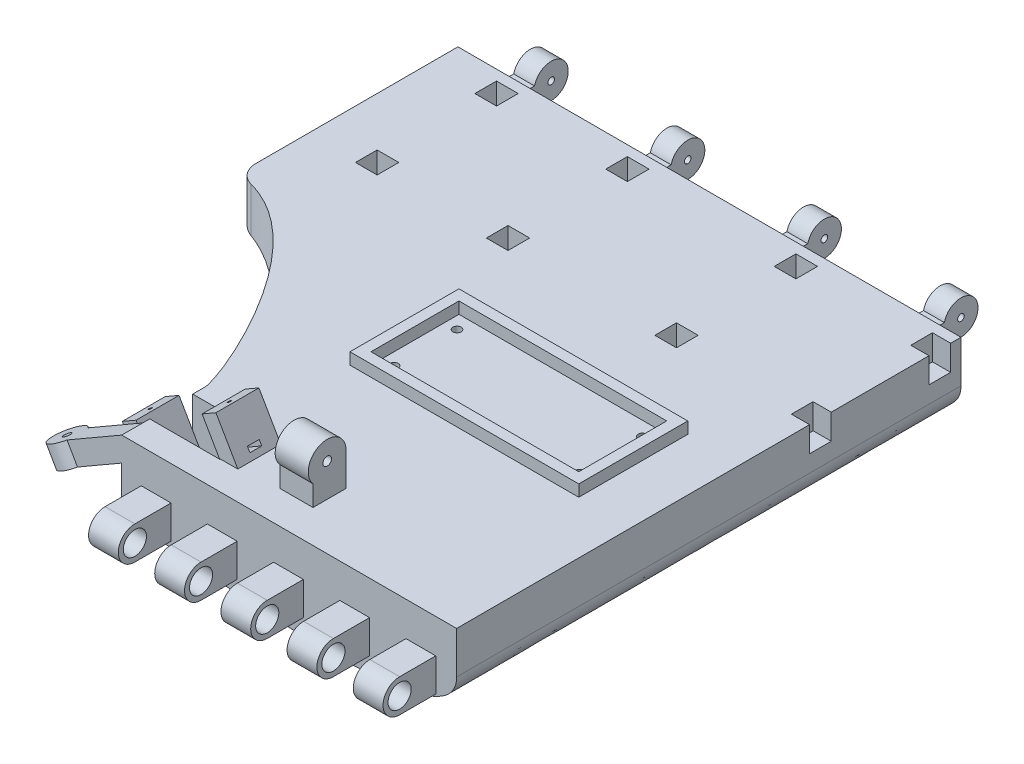
SolidWorks part; units mm, degrees
material "ABS"
ref_plane "Front Plane" through (0, 0, 0) normal (0, 0, 1) x (1, 0, 0)
ref_plane "Top Plane" through (0, 0, 0) normal (0, 1, 0) x (1, 0, 0)
ref_plane "Right Plane" through (0, 0, 0) normal (1, 0, 0) x (0, 0, -1)
sketch "Sketch2" plane through (0, 0, 0) normal (0, 1, 0) x (1, 0, 0)
  line L0 (0, 0) -> (-152, 0)
  line L1 (-152, 0) -> (-152, -152.4)
  line L2 (-152, -152.4) -> (0, -152.4)
  line L3 (0, -152.4) -> (0, 0)
  dimension "D1" = 152.4
  dimension "D2" = 152
extrude "Boss-Extrude2" add sketch "Sketch2" along normal blind 12.7
ref_plane "Plane2" through (-14.9327, 0, 0) normal (1, 0, 0) x (0, 0, -1)
ref_plane "Plane1" through (-12.7, 0, 0) normal (1, 0, 0) x (0, 0, -1)
sketch "Sketch9" plane through (0, 12.7, 0) normal (0, 1, 0) x (1, 0, 0)
  line L0 (0, 0) -> (0, -48.862) construction
  line L1 (0, -152.4) -> (0, 0) construction
  line L2 (-152, 0) -> (-152, -48.862) construction
  line L3 (-152, 0) -> (-152, -152.4) construction
  line L4 (0, 0) -> (-5.4077, 0) construction
  line L5 (0, 0) -> (-152, 0) construction
  dimension "D1" = 48.862
  dimension "D2" = 48.862
  dimension "D3" = 5.4077
ref_axis "Axis2" through (-152, 12.7, 48.862) along (1, 0, 0)
sketch "Sketch3" plane through (-12.7, 0, 0) normal (1, 0, 0) x (0, 0, -1)
  line L0 (0, 6.35) -> (0, 0)
  line L2 (0, 12.7) -> (0, 0) construction
  line L3 (0, 0) -> (12.7, 0)
  line L4 (12.7, 6.1562) -> (12.7, 6.1587)
  line L5 (7.6839, 6.35) -> (0, 6.35)
  arc A3 (12.7, 0) -> (7.6839, 6.35) centre (12.7, 5.1562) ccw
  circle A5 centre (12.7, 5.1562) radius 1
  dimension "D3" = 10.3124
  dimension "D2" = 0
  dimension "D4" = 7.6839
  dimension "D6" = 2
  dimension "D1" = 6.35
  dimension "D5" = 12.7
extrude "Boss-Extrude3" add sketch "Sketch3" against normal blind 6.3 contours A5 L4 L3 A3 | A5 L4 A3 L3 | A3 L5 L0 L3 region at (-12.7, 4.2781, -9.3369)
ref_plane "Plane5" through (0, 0, 24.431) normal (0, 0, -1) x (-1, 0, 0)
ref_plane "Plane6" through (0, 12.7, 0) normal (0, 1, 0) x (1, 0, 0)
sketch "Sketch10" plane through (0, 12.7, 0) normal (0, 1, 0) x (1, 0, 0)
  line L0 (0, 0) -> (-152, 0) construction
  circle A0 centre (-10.2337, -3.175) radius 0.508
  dimension "D1" = 10.2337
  dimension "D3" = 1.016
  dimension "D2" = 3.175
extrude "Cut-Extrude3" [suppressed] cut sketch "Sketch10" against normal blind 9.525
mirror "Mirror1" [suppressed] about plane through (0, 0, 24.431) normal (0, 0, -1)
fillet "Fillet1" radius 1.5875 3 edges at (-19, 3.175, 0) (-15.85, 6.35, 0) (-12.7, 3.175, 0)
pattern_linear "LPattern1" count 4 spacing 41.275 along (-1, 0, 0) of "Boss-Extrude3", "Mirror1", "Fillet1"
sketch "Sketch12" plane through (0, 0, 0) normal (0, 0, -1) x (-1, 0, 0)
  spline S0 degree 1 poles (0, 0) (152, 0) knots 0 0 1 1
  spline S1 degree 2 poles (152, 0) (-0.2287, -25.399) (0, 0) knots 0 0 0 0.553499 0.553499 0.553499
  spline S2 degree 1 poles (0, 0) (152, 0) knots 0 0 1 1
  spline S3 degree 1 poles (152, 0) (0, 0) knots 0 0 1 1
  dimension "D1" = 50.8
extrude "Boss-Extrude4" add sketch "Sketch12" against normal up to surface (152.4 mm away) contours S1 | S0 S1 up to face at (-76, 6.35, 152.4)
sketch "Sketch13" plane through (0, 12.7, 0) normal (0, 1, 0) x (1, 0, 0)
  line L0 (0, -152.4) -> (0, 0) construction
  line L1 (-81.8426, -69.85) -> (-19.05, -69.85)
  line L2 (-81.8426, -69.85) -> (-81.8426, -96.44)
  line L3 (-81.8426, -96.44) -> (-19.05, -96.44)
  line L4 (-19.05, -69.85) -> (-19.05, -96.44)
  line L5 (0, 0) -> (-152, 0) construction
  line L7 (-85.0176, -66.675) -> (-15.875, -66.675)
  line L8 (-85.0176, -66.675) -> (-85.0176, -99.615)
  line L9 (-85.0176, -99.615) -> (-15.875, -99.615)
  line L10 (-15.875, -66.675) -> (-15.875, -99.615)
  dimension "D1" = 62.7926
  dimension "D2" = 26.59
  dimension "D3" = 19.05
  dimension "D4" = 69.85
  dimension "D5" = 3.175
  dimension "D6" = 3.175
  dimension "D7" = 3.175
  dimension "D8" = 3.175
extrude "Boss-Extrude5" add sketch "Sketch13" along normal blind 3.5001
sketch "Sketch14" plane through (0, 12.7, 0) normal (0, 1, 0) x (1, 0, 0)
  line L0 (-19.05, -69.85) -> (-81.8426, -69.85) construction
  line L1 (-81.8426, -69.85) -> (-81.8426, -96.44) construction
  circle A0 centre (-78.1761, -74.1223) radius 1.2497
  circle A1 centre (-22.1767, -74.1223) radius 1.2497
  circle A2 centre (-78.1761, -93.1215) radius 1.2497
  circle A3 centre (-22.1767, -93.1215) radius 1.2497
  dimension "D1" = 4.2723
  dimension "D3" = 3.6665
  dimension "D4" = 55.9994
  dimension "D2" = 18.9992
extrude "Cut-Extrude5" cut sketch "Sketch14" against normal blind 6.35
sketch "Sketch15" plane through (0, 12.7, 0) normal (0, 1, 0) x (1, 0, 0)
  line L0 (-101.2, -152.4) -> (-101.2, -127)
  line L1 (-152, -152.4) -> (0, -152.4) construction
  line L2 (-101.2, -127) -> (-152, -66.4589)
  line L3 (-152, 0) -> (-152, -152.4) construction
  line L4 (-152, -66.4589) -> (-152, -152.4)
  line L5 (-152, -152.4) -> (-101.2, -152.4)
  spline S0 degree 3 poles (-101.2, -127) (-102.2273, -119.2728) (-124.4228, -68.0569) (-152, -66.4589) knots 0 0 0 0 0.841715 0.841715 0.841715 0.841715
  line M9 (-152, 0) -> (-152, -152.4)
  line M10 (-152, -152.4) -> (0, -152.4)
  dimension "D1" = 50.8
  dimension "D2" = 25.4
  dimension "D3" = 220
extrude "Cut-Extrude6" cut sketch "Sketch15" against normal through all contours L2 S0 | L0 L2 M9 M10 region at (-131.2037, 12.7, 121.8215) region at (-125.4187, 12.7, 91.8783)
sketch "Sketch16" plane through (0, 0, 152.4) normal (0, 0, 1) x (1, 0, 0)
  line L0 (-101.2, 12.7) -> (-101.2, 5.3677)
  line L1 (-101.2, 12.7) -> (-117.6978, 3.175)
  line L2 (-101.2, 5.3677) -> (-117.6978, -4.1573)
  line L3 (-117.6978, 3.175) -> (-117.6978, -4.1573)
  line L4 (-101.2, -7.6194) -> (-101.2, 12.7) construction
  dimension "D1" = 6.35
  dimension "D2" = 60
  dimension "D3" = 19.05
extrude "Boss-Extrude6" add sketch "Sketch16" against normal blind 6.35
sketch "Sketch17" plane through (-27.6243, 47.8466, 0) normal (0.5, -0.866, 0) x (0.866, 0.5, 0)
  line L0 (-104.0079, 146.05) -> (-104.0079, 152.4) construction
  circle A0 centre (-104.0079, 149.225) radius 4.826
  dimension "D1" = 9.652
extrude "Boss-Extrude7" add sketch "Sketch17" against normal up to surface (6.35 mm away) up to face at (-109.4489, 7.9375, 149.225)
sketch "Sketch18" plane through (-27.6243, 47.8466, 0) normal (0.5, -0.866, 0) x (0.866, 0.5, 0)
  circle A0 centre (-104.0079, 149.225) radius 1.143
  dimension "D1" = 2.286
extrude "Cut-Extrude8" cut sketch "Sketch18" against normal up to surface (6.35 mm away) up to face at (-113.4243, 5.6423, 149.225)
ref_plane "Plane7" through (-30.7993, 53.3459, 0) normal (-0.5, 0.866, 0) x (0.866, 0.5, 0)
sketch "Sketch20" plane through (-30.7993, 53.3459, 0) normal (-0.5, 0.866, 0) x (0.866, 0.5, 0)
  line L0 (-86.0567, -130.9381) -> (-86.0567, -143.9239)
  line L1 (-86.0567, -143.9239) -> (-62.911, -143.9239)
  line L2 (-62.911, -143.9239) -> (-62.911, -130.9381)
  line L3 (-62.911, -130.9381) -> (-86.0567, -130.9381)
  dimension "D1" = 12.9857
  dimension "D2" = 23.1457
extrude "Cut-Extrude9" cut sketch "Sketch20" against normal blind 15.494
sketch "Sketch21" plane through (-30.7993, 53.3459, 0) normal (-0.5, 0.866, 0) x (0.866, 0.5, 0)
  line L0 (-86.0373, -130.9653) -> (-90.8633, -130.9653)
  line L1 (-90.8633, -130.9653) -> (-90.8633, -143.951)
  line L2 (-90.8633, -143.951) -> (-86.0373, -143.951)
  line L3 (-86.0373, -143.951) -> (-86.0373, -130.9653)
  line L4 (-63.2251, -143.7536) -> (-58.3991, -143.7536)
  line L5 (-58.3991, -143.7536) -> (-58.3991, -130.7678)
  line L6 (-58.3991, -130.7678) -> (-63.2251, -130.7678)
  line L7 (-63.2251, -130.7678) -> (-63.2251, -143.7536)
  line L8 (6.35, -152.4) -> (6.35, 0) construction
  dimension "D1" = 12.9857
  dimension "D2" = 12.9857
  dimension "D3" = 4.826
  dimension "D4" = 22.8122
  dimension "D5" = 4.826
  dimension "D6" = 64.7491
extrude "Boss-Extrude8" add sketch "Sketch21" against normal up to surface (18.046 mm away) up to face at (-89.1246, -1.8694, 79.9709)
sketch "Sketch22" plane through (-30.7993, 53.3459, 0) normal (-0.5, 0.866, 0) x (0.866, 0.5, 0)
  circle A0 centre (-88.4503, -137.587) radius 0.508
  circle A1 centre (-60.8121, -137.587) radius 0.508
  dimension "D1" = 1.016
  dimension "D2" = 1.016
extrude "Cut-Extrude10" cut sketch "Sketch22" against normal blind 10.16
sketch "Esquisse1" plane through (0, 0, 152.4) normal (0, 0, 1) x (1, 0, 0)
  line L0 (-78.1, 4.563) -> (-78.1, 7.7177)
  line L1 (-74.3, 4.1474) -> (-74.3, 7.7177)
  line L2 (-78.1, 4.563) -> (-92.8263, 3.2599)
  line L3 (-92.8263, -0.7245) -> (-78.1, -2.0277)
  line L4 (-78.1, -2.0277) -> (-78.1, -5.1823)
  line L5 (-74.3, -5.1823) -> (-74.3, -1.612)
  line L6 (-73.9909, -1.3823) -> (-62.0409, -0.7293)
  line L7 (-73.9909, 3.9177) -> (-62.0409, 3.2647)
  arc A0 (-78.1, 7.7177) -> (-74.3, 7.7177) centre (-76.2, 7.7177) cw
  arc A2 (-62.0409, 3.2647) -> (-62.0409, -0.7293) centre (-62.15, 1.2677) cw
  arc A3 (-92.8263, 3.2599) -> (-92.8263, -0.7245) centre (-92.65, 1.2677) ccw
  arc A4 (-78.1, -5.1823) -> (-74.3, -5.1823) centre (-76.2, -5.1823) ccw
  arc A5 (-74.3, 4.1474) -> (-73.9909, 3.9177) centre (-76.2, 1.2677) cw
  arc A6 (-73.9909, -1.3823) -> (-74.3, -1.612) centre (-76.2, 1.2677) cw
fillet "Fillet2" radius 6.35 2 edges at (-101.2, 2.5403, 127) (-152, 6.35, 66.4589)
sketch "Sketch23" plane through (-50.5751, -29.1996, 0) normal (0.866, 0.5, 0) x (0, 0, -1)
  line L0 (-139.1816, 51.6925) -> (-139.1816, 50.1685)
  line L1 (-139.1816, 50.1685) -> (-135.6256, 50.1685)
  line L2 (-135.6256, 50.1685) -> (-135.6256, 51.6925)
  line L3 (-135.6256, 51.6925) -> (-139.1816, 51.6925)
  line L4 (-143.7536, 61.5985) -> (-130.7678, 61.5985) construction
  line L5 (-143.7536, 48.3814) -> (-143.7536, 61.5985) construction
  dimension "D1" = 9.906
  dimension "D2" = 4.572
  dimension "D3" = 3.556
  dimension "D4" = 1.524
extrude "Cut-Extrude11" cut sketch "Sketch23" against normal up to surface (4.826 mm away) up to face at (-81.233, 14.2495, 135.1532)
sketch "Esquisse5" plane through (0, 12.7, 0) normal (0, 1, 0) x (1, 0, 0)
  line L0 (-130.7715, -45.6452) -> (-137.1215, -45.6452) construction
  line L1 (-137.1215, -45.6452) -> (-137.1215, -39.2952) construction
  line L2 (-137.1215, -39.2952) -> (-130.7715, -39.2952) construction
  line L3 (-130.7715, -39.2952) -> (-130.7715, -45.6452) construction
  line L4 (-130.7715, -9.5674) -> (-137.1215, -9.5674) construction
  line L5 (-137.1215, -9.5674) -> (-137.1215, -3.2174) construction
  line L6 (-137.1215, -3.2174) -> (-130.7715, -3.2174) construction
  line L7 (-130.7715, -3.2174) -> (-130.7715, -9.5674) construction
  line L8 (-130.7715, -45.6452) -> (-137.1215, -45.6452) construction
  line L9 (-137.1215, -45.6452) -> (-137.1215, -39.2952) construction
  line L10 (-137.1215, -39.2952) -> (-130.7715, -39.2952) construction
  line L11 (-130.7715, -39.2952) -> (-130.7715, -45.6452) construction
  line L12 (-130.7715, -9.5674) -> (-137.1215, -9.5674) construction
  line L13 (-137.1215, -9.5674) -> (-137.1215, -3.2174) construction
  line L14 (-137.1215, -3.2174) -> (-130.7715, -3.2174) construction
  line L15 (-130.7715, -3.2174) -> (-130.7715, -9.5674) construction
  line L16 (-137.2215, -3.1174) -> (-130.6715, -3.1174)
  line L17 (-130.6715, -3.1174) -> (-130.6715, -9.6674)
  line L18 (-130.6715, -9.6674) -> (-137.2215, -9.6674)
  line L19 (-137.2215, -9.6674) -> (-137.2215, -3.1174)
  line L20 (-137.2215, -39.1952) -> (-130.6715, -39.1952)
  line L21 (-130.6715, -39.1952) -> (-130.6715, -45.7452)
  line L22 (-130.6715, -45.7452) -> (-137.2215, -45.7452)
  line L23 (-137.2215, -45.7452) -> (-137.2215, -39.1952)
  dimension "D1" = 0.1
extrude "Enlèv. mat.-Extru.3" cut sketch "Esquisse5" against normal blind 7.62
sketch "Esquisse6" plane through (0, 0, 152.4) normal (0, 0, 1) x (1, 0, 0)
  line L5 (-55.3, -7.62) -> (-46.3, -7.62)
  line L6 (-55.3, -7.62) -> (-55.3, 2.38)
  line L7 (-55.3, 2.38) -> (-46.3, 2.38)
  line L8 (-46.3, -7.62) -> (-46.3, 2.38)
  line L10 (0, 12.7) -> (0, 0) construction
  point P9 (-50.8, 2.38)
  dimension "D1" = 9
  dimension "D2" = 10
  dimension "D3" = 7.62
  dimension "D4" = 50.8
extrude "Boss.-Extru.1" add sketch "Esquisse6" along normal blind 10.922
sketch "Esquisse7" plane through (-55.3, 0, 0) normal (-1, 0, 0) x (0, 0, 1)
  line L1 (163.322, 2.38) -> (163.322, -7.62) construction
  circle A0 centre (163.322, -2.62) radius 5
extrude "Boss.-Extru.2" add sketch "Esquisse7" against normal up to surface (9 mm away) up to face at (-46.3, -2.62, 157.861)
hole_wizard "Dégagement M21" positions "Esquisse8" profile "Esquisse9" hole size "M2" standard "Ansi Metric" end condition up to next
sketch "Esquisse8" plane through (-55.3, 0, 0) normal (-1, 0, 0) x (0, 0, 1)
  line L1 (152.4, 2.38) -> (152.4, -7.62) construction
  point P0 (163.322, -2.62)
  point P15 (152.4, -2.62)
sketch "Esquisse9" plane through (-55.3, -2.62, 163.322) normal (0, 1, 0) x (0, 0, 1)
  line L0 (0, 0) -> (0, 9)
  line L1 (0, 9) -> (3.5, 9)
  line L2 (3.5, 9) -> (3.5, 0)
  line L5 (3.5, 0) -> (0, 0)
  line L11 (0, -6.35) -> (0, 107.95) construction
  dimension "Diamètre du perçage jusqu'au prochain" = 7
  dimension "Profondeur du perçage jusqu'au prochain" = 9
pattern_linear "Répétition linéaire1" count 3 spacing 20 along (1, 0, 0) count 3 spacing 20 along (-1, 0, 0) of "Boss.-Extru.1", "Dégagement M21", "Boss.-Extru.2" pattern seed only yes
sketch "Esquisse10" plane through (0, 12.7, 0) normal (0, -1, 0) x (1, 0, 0)
  line L1 (-53.34, 142.4581) -> (-63.34, 142.4581)
  line L2 (-53.34, 142.4581) -> (-53.34, 132.4581)
  line L3 (-53.34, 132.4581) -> (-63.34, 132.4581)
  line L4 (-63.34, 142.4581) -> (-63.34, 132.4581)
  line L5 (-55.3, 152.4) -> (-46.3, 152.4) construction
  line L6 (-101.2, 143.951) -> (-101.2, 130.9653) construction
  point P4 (-63.34, 137.4581)
  point P8 (-50.8, 152.4)
  point P10 (-101.2, 137.4581)
  dimension "D1" = 10
  dimension "D2" = 10
  dimension "D3" = 2.54
extrude "Boss.-Extru.3" add sketch "Esquisse10" against normal blind 10
sketch "Esquisse11" plane through (-53.34, 0, 0) normal (1, 0, 0) x (0, 0, -1)
  line L0 (-132.4581, 22.7) -> (-142.4581, 22.7) construction
  circle A0 centre (-138.1731, 22.7) radius 5.715
  dimension "D1" = 11.43
extrude "Boss.-Extru.4" add sketch "Esquisse11" against normal up to surface (10 mm away) up to face at (-63.34, 17.7, 137.4581)
sketch "Esquisse13" plane through (-53.34, 0, 0) normal (1, 0, 0) x (0, 0, -1)
  circle A0 centre (-138.1731, 22.7) radius 1.3
  arc A2 (-132.4581, 22.7) -> (-142.4581, 18.9185) centre (-138.1731, 22.7) ccw construction
  dimension "D1" = 2.6
extrude "Enlèv. mat.-Extru.4" cut sketch "Esquisse13" against normal up to next
sketch "Esquisse14" plane through (0, 12.7, 0) normal (0, 1, 0) x (1, 0, 0)
  line L0 (-91.2294, -39.2952) -> (-91.2294, -45.6452) construction
  line L1 (-91.2294, -45.6452) -> (-97.5794, -45.6452) construction
  line L2 (-97.5794, -45.6452) -> (-97.5794, -39.2952) construction
  line L3 (-97.5794, -39.2952) -> (-91.2294, -39.2952) construction
  line L4 (-46.6615, -45.6452) -> (-46.6615, -39.2952) construction
  line L5 (-40.3115, -45.6452) -> (-46.6615, -45.6452) construction
  line L6 (-40.3115, -39.2952) -> (-40.3115, -45.6452) construction
  line L7 (-46.6615, -39.2952) -> (-40.3115, -39.2952) construction
  line L8 (-5.3865, -45.6455) -> (-5.3865, -39.2955) construction
  line L9 (-5.3865, -39.2955) -> (0.9635, -39.2955) construction
  line L10 (0.9635, -39.2955) -> (0.9635, -45.6455) construction
  line L11 (0.9635, -45.6455) -> (-5.3865, -45.6455) construction
  line L12 (0.9635, -9.5677) -> (-5.3865, -9.5677) construction
  line L13 (-5.3865, -9.5677) -> (-5.3865, -3.2177) construction
  line L14 (-5.3865, -3.2177) -> (0.9635, -3.2177) construction
  line L15 (0.9635, -3.2177) -> (0.9635, -9.5677) construction
  line L16 (-40.3115, -3.2174) -> (-40.3115, -9.5674) construction
  line L17 (-46.6615, -3.2174) -> (-40.3115, -3.2174) construction
  line L18 (-46.6615, -9.5674) -> (-46.6615, -3.2174) construction
  line L19 (-40.3115, -9.5674) -> (-46.6615, -9.5674) construction
  line L20 (-91.2294, -9.5674) -> (-97.5794, -9.5674) construction
  line L21 (-91.2294, -3.2174) -> (-91.2294, -9.5674) construction
  line L22 (-97.5794, -3.2174) -> (-91.2294, -3.2174) construction
  line L23 (-97.5794, -9.5674) -> (-97.5794, -3.2174) construction
  line L24 (-91.2294, -39.2952) -> (-91.2294, -45.6452) construction
  line L25 (-91.2294, -45.6452) -> (-97.5794, -45.6452) construction
  line L26 (-97.5794, -45.6452) -> (-97.5794, -39.2952) construction
  line L27 (-97.5794, -39.2952) -> (-91.2294, -39.2952) construction
  line L28 (-46.6615, -45.6452) -> (-46.6615, -39.2952) construction
  line L29 (-40.3115, -45.6452) -> (-46.6615, -45.6452) construction
  line L30 (-40.3115, -39.2952) -> (-40.3115, -45.6452) construction
  line L31 (-46.6615, -39.2952) -> (-40.3115, -39.2952) construction
  line L32 (-5.3865, -45.6455) -> (-5.3865, -39.2955) construction
  line L33 (-5.3865, -39.2955) -> (0.9635, -39.2955) construction
  line L34 (0.9635, -39.2955) -> (0.9635, -45.6455) construction
  line L35 (0.9635, -45.6455) -> (-5.3865, -45.6455) construction
  line L36 (0.9635, -9.5677) -> (-5.3865, -9.5677) construction
  line L37 (-5.3865, -9.5677) -> (-5.3865, -3.2177) construction
  line L38 (-5.3865, -3.2177) -> (0.9635, -3.2177) construction
  line L39 (0.9635, -3.2177) -> (0.9635, -9.5677) construction
  line L40 (-40.3115, -3.2174) -> (-40.3115, -9.5674) construction
  line L41 (-46.6615, -3.2174) -> (-40.3115, -3.2174) construction
  line L42 (-46.6615, -9.5674) -> (-46.6615, -3.2174) construction
  line L43 (-40.3115, -9.5674) -> (-46.6615, -9.5674) construction
  line L44 (-91.2294, -9.5674) -> (-97.5794, -9.5674) construction
  line L45 (-91.2294, -3.2174) -> (-91.2294, -9.5674) construction
  line L46 (-97.5794, -3.2174) -> (-91.2294, -3.2174) construction
  line L47 (-97.5794, -9.5674) -> (-97.5794, -3.2174) construction
  line L48 (-91.1294, -39.1952) -> (-91.1294, -45.7452)
  line L49 (-91.1294, -45.7452) -> (-97.6794, -45.7452)
  line L50 (-97.6794, -45.7452) -> (-97.6794, -39.1952)
  line L51 (-97.6794, -39.1952) -> (-91.1294, -39.1952)
  line L52 (-46.7615, -45.7452) -> (-46.7615, -39.1952)
  line L53 (-46.7615, -39.1952) -> (-40.2115, -39.1952)
  line L54 (-40.2115, -39.1952) -> (-40.2115, -45.7452)
  line L55 (-40.2115, -45.7452) -> (-46.7615, -45.7452)
  line L56 (-5.4865, -45.7455) -> (-5.4865, -39.1955)
  line L57 (-5.4865, -39.1955) -> (1.0635, -39.1955)
  line L58 (1.0635, -39.1955) -> (1.0635, -45.7455)
  line L59 (1.0635, -45.7455) -> (-5.4865, -45.7455)
  line L60 (1.0635, -9.6677) -> (-5.4865, -9.6677)
  line L61 (-5.4865, -9.6677) -> (-5.4865, -3.1177)
  line L62 (-5.4865, -3.1177) -> (1.0635, -3.1177)
  line L63 (1.0635, -3.1177) -> (1.0635, -9.6677)
  line L64 (-40.2115, -3.1174) -> (-40.2115, -9.6674)
  line L65 (-40.2115, -9.6674) -> (-46.7615, -9.6674)
  line L66 (-46.7615, -9.6674) -> (-46.7615, -3.1174)
  line L67 (-46.7615, -3.1174) -> (-40.2115, -3.1174)
  line L68 (-91.1294, -9.6674) -> (-97.6794, -9.6674)
  line L69 (-97.6794, -9.6674) -> (-97.6794, -3.1174)
  line L70 (-97.6794, -3.1174) -> (-91.1294, -3.1174)
  line L71 (-91.1294, -3.1174) -> (-91.1294, -9.6674)
  dimension "D1" = 0.1
extrude "Enlèv. mat.-Extru.5" cut sketch "Esquisse14" against normal blind 7.62
